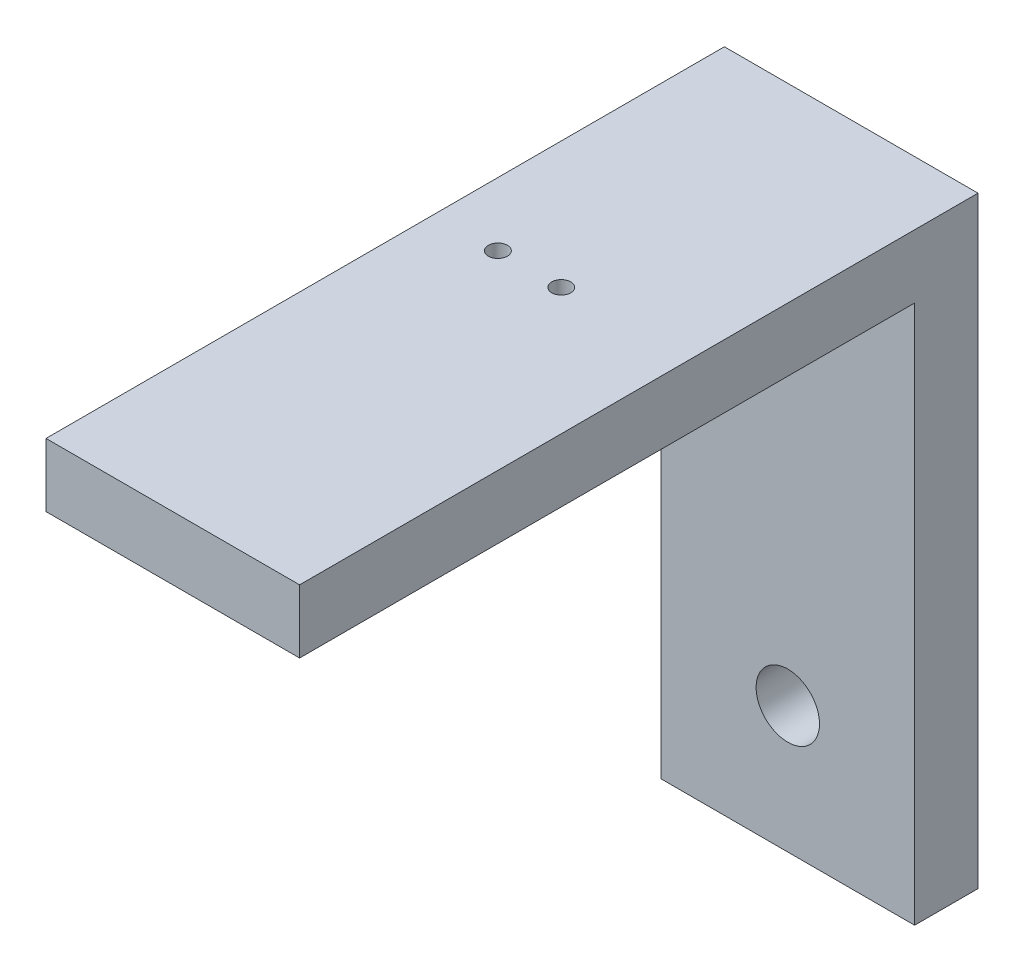
SolidWorks part; units mm, degrees
ref_plane "前视基准面" through (0, 0, 0) normal (0, 0, 1) x (1, 0, 0)
ref_plane "上视基准面" through (0, 0, 0) normal (0, 1, 0) x (1, 0, 0)
ref_plane "右视基准面" through (0, 0, 0) normal (1, 0, 0) x (0, 0, -1)
sketch "草图1" plane through (0, 0, 0) normal (0, 0, 1) x (1, 0, 0)
  circle A0 centre (0, 0) radius 5
  dimension "D1" = 10
sketch "草图2" plane through (0, 0, 0) normal (0, 0, 1) x (1, 0, 0)
  line L0 (0, 20) -> (0, -20) construction
  point P4 (0, 0)
  dimension "D1" = 40
sketch "草图4" plane through (0, 0, 0) normal (0, 0, 1) x (1, 0, 0)
  line L0 (-20, 20) -> (20, 20)
  line L1 (-20, 20) -> (-20, -20)
  line L2 (-20, -20) -> (20, -20)
  line L3 (20, -20) -> (20, 20)
  point P0 (0, 20)
  point P5 (0, 20)
extrude "凸台-拉伸1" add sketch "草图4" along normal blind 10
extrude "切除-拉伸1" cut sketch "草图1" along normal blind 19 contours A0
sketch "草图5" plane through (0, 20, 0) normal (0, 1, 0) x (1, 0, 0)
  line L0 (20, -10) -> (-20, -10) construction
  line L1 (-20, 0) -> (20, 0)
  line L2 (-20, 0) -> (-20, -10)
  line L3 (-20, -10) -> (20, -10)
  line L4 (20, 0) -> (20, -10)
extrude "凸台-拉伸2" add sketch "草图5" along normal blind 55 contours L1 L4 L3 L2
sketch "草图6" plane through (0, 0, 10) normal (0, 0, 1) x (1, 0, 0)
  line L0 (20, -20) -> (20, 75) construction
  line L1 (-20, 75) -> (20, 75)
  line L2 (-20, 75) -> (-20, 65)
  line L3 (-20, 65) -> (20, 65)
  line L4 (20, 75) -> (20, 65)
  dimension "D1" = 10
extrude "凸台-拉伸3" add sketch "草图6" along normal blind 97 contours L3 L4 L1 L2
sketch "草图7" plane through (0, 75, 0) normal (0, 1, 0) x (1, 0, 0)
  circle A0 centre (0, -45.7294) radius 1.5
  dimension "D1" = 3
extrude "切除-拉伸2" cut sketch "草图7" against normal blind 17 contours A0
pattern_linear "阵列(线性)1" count 2 spacing 10 along (-1, 0, 0) of "切除-拉伸2"
ref_axis "基准轴1" through (0, 0, 112.45) along (0, 0, -1)
sketch "草图10" plane through (0, 0, 0) normal (0, 0, 1) x (1, 0, 0)
  circle A0 centre (0, -10.3794) radius 1
  dimension "D1" = 2
extrude "凸台-拉伸5" add sketch "草图10" against normal blind 2 contours A0
pattern_circular "阵列(圆周)3" count 4 over 360 about axis through (0, 0, 0) along (0, 0, 1) of "凸台-拉伸5"
draft "拔模2" type of draft neutral plane draft angle 15 faces to draft 1 face at (1, -10.3794, -2) neutral plane through (0, -10.3794, -2) neutral plane normal (0, 0, -1) parameters "D1"=15
draft "拔模3" type of draft neutral plane draft angle 15 faces to draft 1 face at (10.3794, 1, -2) neutral plane through (10.3794, 0, -2) neutral plane normal (0, 0, -1) parameters "D1"=15
draft "拔模4" type of draft neutral plane draft angle 15 faces to draft 1 face at (-1, 10.3794, -2) neutral plane through (0, 10.3794, -2) neutral plane normal (0, 0, -1) parameters "D1"=15
draft "拔模5" type of draft neutral plane draft angle 15 faces to draft 1 face at (-10.3794, -1, -2) neutral plane through (-10.3794, 0, -2) neutral plane normal (0, 0, -1) parameters "D1"=15
